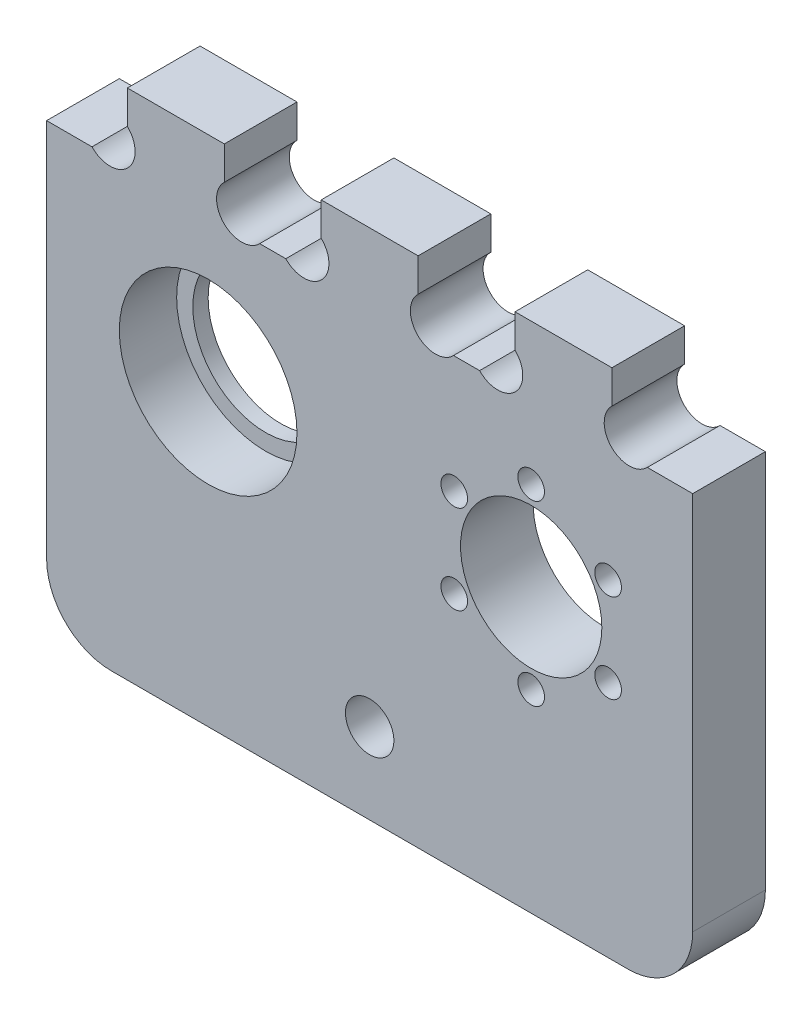
SolidWorks part; units mm, degrees
ref_plane "Front" through (0, 0, 0) normal (0, 0, 1) x (1, 0, 0)
ref_plane "Top" through (0, 0, 0) normal (0, 1, 0) x (1, 0, 0)
ref_plane "Right" through (0, 0, 0) normal (1, 0, 0) x (0, 0, -1)
sketch "Esquisse1" plane through (0, 0, 0) normal (0, 0, 1) x (1, 0, 0)
  line L1 (0, 0) -> (80, 0)
  line L2 (0, 0) -> (0, 55)
  line L3 (0, 55) -> (80, 55)
  line L4 (80, 0) -> (80, 55)
  dimension "D1" = 55
  dimension "D2" = 80
extrude "Boss.-Extru.1" add sketch "Esquisse1" along normal blind 9
sketch "Esquisse2" plane through (0, 0, 9) normal (0, 0, 1) x (1, 0, 0)
  line L0 (20, 55) -> (20, 0) construction
  line L1 (80, 55) -> (0, 55) construction
  line L2 (0, 0) -> (80, 0) construction
  line L4 (60, 35) -> (60, 55) construction
  line L6 (0, 55) -> (0, 0) construction
  circle A0 centre (20, 37) radius 11
  circle A1 centre (60, 35) radius 8.75
  circle A2 centre (60, 46) radius 1.65
  circle A3 centre (69.5263, 40.5) radius 1.65
  circle A4 centre (69.5263, 29.5) radius 1.65
  circle A5 centre (60, 24) radius 1.65
  circle A6 centre (50.4737, 29.5) radius 1.65
  circle A7 centre (50.4737, 40.5) radius 1.65
  point P29 (60, 35)
  dimension "D1" = 22
  dimension "D2" = 18
  dimension "D4" = 17.5
  dimension "D7" = 3.3
  dimension "D3" = 20
  dimension "D5" = 20
  dimension "D6" = 20
  dimension "D8" = 11
  dimension "D9" = 6
extrude "Enlèv. mat.-Extru.1" cut sketch "Esquisse2" against normal through all
sketch "Esquisse3" plane through (0, 0, 9) normal (0, 0, 1) x (1, 0, 0)
  circle A0 centre (40, 10) radius 3
  circle A1 centre (60, 35) radius 8.75 construction
  dimension "D3" = 6
  dimension "D1" = 25
  dimension "D2" = 20
extrude "Enlèv. mat.-Extru.2" cut sketch "Esquisse3" against normal through all
fillet "Congé1" radius 8 2 edges at (0, 0, 4.5) (80, 0, 4.5)
sketch "Esquisse4" plane through (0, 0, 0) normal (0, 0, 1) x (1, 0, 0)
  circle A0 centre (20, 37) radius 11
  circle A1 centre (20, 37) radius 9
  dimension "D1" = 22
  dimension "D2" = 2
extrude "Boss.-Extru.2" add sketch "Esquisse4" along normal blind 1.9
sketch "Esquisse5" plane through (0, 0, 9) normal (0, 0, 1) x (1, 0, 0)
  line L0 (40, 0) -> (40, 55) construction
  line L1 (8, 0) -> (72, 0) construction
  line L2 (80, 55) -> (0, 55) construction
  line L3 (46, 55) -> (34, 55)
  line L4 (34, 55) -> (34, 63.5)
  line L5 (34, 63.5) -> (46, 63.5)
  line L6 (40, 63.5) -> (40, 55) construction
  line L7 (46, 55) -> (46, 63.5)
  line L8 (34, 55) -> (22, 55) construction
  line L9 (28, 55) -> (28, 69.0362) construction
  line L10 (16, 63.5) -> (16, 55) construction
  line L11 (10, 55) -> (10, 63.5)
  line L12 (22, 63.5) -> (10, 63.5)
  line L13 (22, 55) -> (22, 63.5)
  line L14 (10, 55) -> (22, 55)
  line L15 (64, 63.5) -> (64, 55) construction
  line L16 (70, 55) -> (58, 55)
  line L17 (58, 55) -> (58, 63.5)
  line L18 (58, 63.5) -> (70, 63.5)
  line L19 (70, 55) -> (70, 63.5)
  dimension "D1" = 6
  dimension "D2" = 8.5
  dimension "D3" = 12
extrude "Boss.-Extru.3" add sketch "Esquisse5" against normal up to vertex (9 mm away) up to point (0, 55, 0)
sketch "Esquisse6" plane through (0, 0, 9) normal (0, 0, 1) x (1, 0, 0)
  line L0 (40, 0) -> (40, 63.5) construction
  line L1 (8, 0) -> (72, 0) construction
  line L2 (46, 63.5) -> (34, 63.5) construction
  line L3 (34, 55) -> (34, 54.9) construction
  line L4 (34, 55) -> (34.1, 55) construction
  line L5 (28, 55) -> (28, 63.5) construction
  line L6 (34, 55) -> (22, 55) construction
  line L7 (22, 55) -> (21.9, 55) construction
  line L8 (22, 55) -> (22, 54.9) construction
  line L9 (16, 63.5) -> (16, 54.0047) construction
  line L10 (22, 63.5) -> (10, 63.5) construction
  line L11 (10, 55) -> (10, 54.9) construction
  line L12 (10, 55) -> (10.1, 55) construction
  line L13 (70, 55) -> (69.9, 55) construction
  line L14 (70, 55) -> (70, 54.9) construction
  line L15 (58, 55) -> (58, 54.9) construction
  line L16 (58, 55) -> (58.1, 55) construction
  line L17 (46, 55) -> (45.9, 55) construction
  line L18 (46, 55) -> (46, 54.9) construction
  circle A0 centre (31.8585, 57.1415) radius 3.1
  circle A1 centre (24.1415, 57.1415) radius 3.1
  circle A2 centre (7.8585, 57.1415) radius 3.1
  circle A3 centre (72.1415, 57.1415) radius 3.1
  circle A4 centre (55.8585, 57.1415) radius 3.1
  circle A5 centre (48.1415, 57.1415) radius 3.1
  dimension "D2" = 6.2
  dimension "D1" = 0.1
extrude "Enlèv. mat.-Extru.3" cut sketch "Esquisse6" against normal through all both and the other way through all
